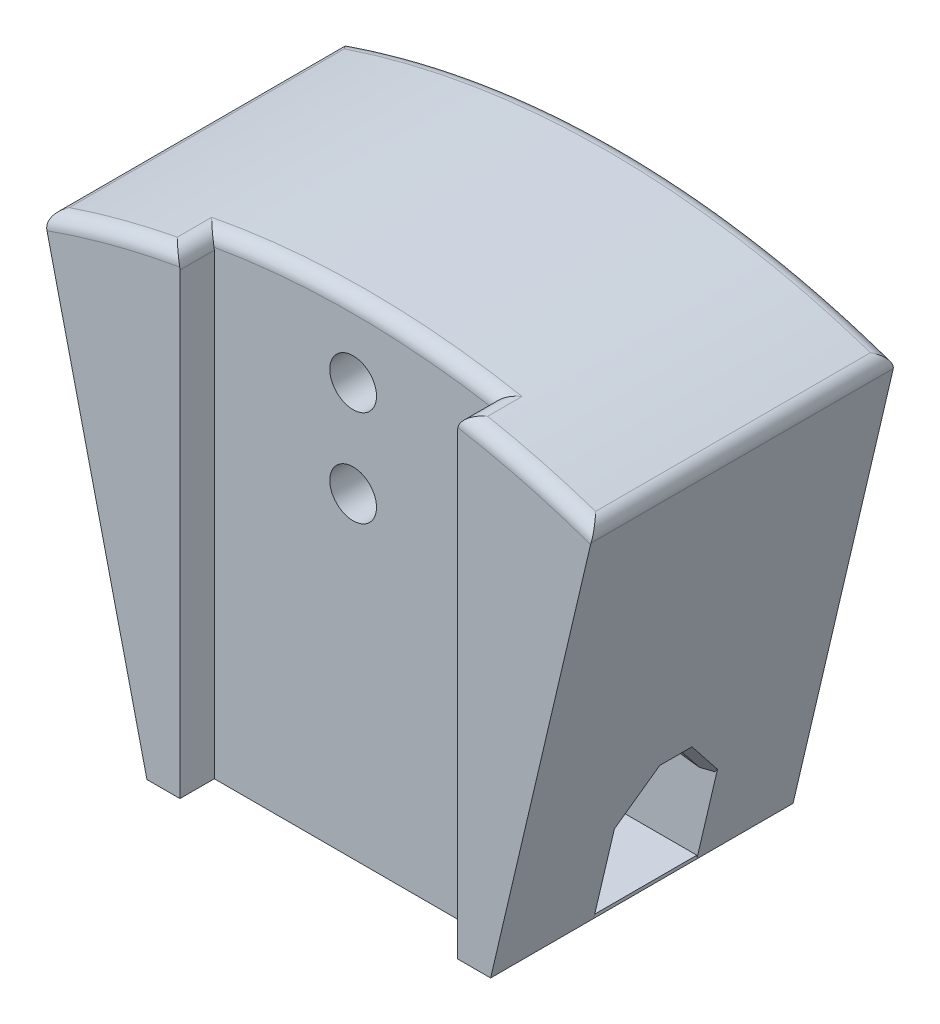
SolidWorks part; units mm, degrees
ref_plane "Front Plane" through (0, 0, 0) normal (0, 0, 1) x (1, 0, 0)
ref_plane "Top Plane" through (0, 0, 0) normal (0, 1, 0) x (1, 0, 0)
ref_plane "Right Plane" through (0, 0, 0) normal (1, 0, 0) x (0, 0, -1)
sketch "Sketch1" plane through (0, 0, 0) normal (0, 0, 1) x (1, 0, 0)
  line L3 (-15.875, -12.7) -> (-25.4, 27.8365)
  line L6 (15.875, -12.7) -> (-15.875, -12.7)
  line L8 (0, 0) -> (-15.875, -12.7) construction
  line L9 (15.875, -12.7) -> (0, 0) construction
  line L10 (15.875, -12.7) -> (25.4, 27.8365)
  line L12 (0, 0) -> (0, 32.1945) construction
  arc A0 (-25.4, 27.8365) -> (25.4, 27.8365) centre (0, -44.0055) cw
  point P3 (0, 0)
  point P8 (0, 0)
  point P12 (0, 32.1945)
  dimension "D1" = 32.1945
  dimension "D3" = 50.8
  dimension "D8" = 102.68
  dimension "D2" = 76.2
  dimension "D5" = 31.75
  dimension "D6" = 12.7
extrude "Boss-Extrude1" add sketch "Sketch1" along normal mid plane 27.94
sketch "Sketch5" plane through (0, 0, 13.97) normal (0, 0, 1) x (1, 0, 0)
  line L4 (0, -12.7) -> (0, 0) construction
  line L5 (-12.827, 0) -> (12.827, 0) construction
  line L8 (-12.827, 63.5) -> (-12.827, -12.7)
  line L9 (-12.827, -12.7) -> (12.827, -12.7)
  line L10 (12.827, -12.7) -> (12.827, 63.5)
  line L11 (12.827, 63.5) -> (-12.827, 63.5)
  point P9 (0, 0)
  dimension "D1" = 25.654
  dimension "D2" = 76.2
  dimension "D3" = 12.7
extrude "Cut-Extrude3" cut sketch "Sketch5" against normal blind 3.175
sketch "Sketch8" plane through (0, 0, 10.795) normal (0, 0, 1) x (1, 0, 0)
  line L0 (0, 25.4) -> (0, 0) construction
  circle A2 centre (0, 16.51) radius 2.159
  circle A4 centre (0, 25.4) radius 2.159
  dimension "D2" = 16.51
  dimension "D3" = 4.318
  dimension "D1" = 25.4
extrude "Cut-Extrude5" cut sketch "Sketch8" against normal through all both and the other way through all
ref_axis "Axis1" through (0, 0, 20.955) along (0, 0, -1)
sketch "Sketch6" plane through (0, 0, 0) normal (1, 0, 0) x (0, 0, -1)
  line L1 (-4.445, 13.97) -> (5.08, 13.97)
  line L5 (-20.955, 0) -> (20.955, 0) construction
  line L7 (5.08, 13.97) -> (5.08, 0)
  line L8 (5.08, 0) -> (-4.445, 0)
  line L9 (-4.445, 0) -> (-4.445, 13.97)
  line L11 (-10.795, 32.1945) -> (-10.795, 31.1071) construction
  dimension "D1" = 6.35
  dimension "D2" = 13.97
  dimension "D3" = 9.525
revolve "Cut-Revolve2" cut sketch "Sketch6" angle 360 about axis through (0, 0, 20.955) along (0, 0, -1)
ref_plane "Plane1" through (0, 0, -0.3175) normal (0, 0, -1) x (-1, 0, 0)
sketch "Sketch7" plane through (0, 0, -5.08) normal (0, 0, -1) x (-1, 0, 0)
  line L0 (12.8382, 5.5083) -> (17.5649, -5.5083)
  line L2 (-12.8382, 5.5083) -> (-17.5649, -5.5083)
  line L3 (25.4, 27.8365) -> (15.875, -12.7) construction
  line L5 (17.5649, -5.5083) -> (15.875, -12.7)
  line L6 (15.875, -12.7) -> (-15.875, -12.7)
  line L7 (-15.875, -12.7) -> (-17.5649, -5.5083)
  line L8 (-15.875, -12.7) -> (-25.4, 27.8365) construction
  line L9 (15.2015, 0) -> (-15.2015, 0) construction
  line L10 (-15.875, -12.7) -> (-25.4, 27.8365) construction
  arc A4 (5.8199, -12.7) -> (-5.8199, -12.7) centre (0, 0) ccw construction
  arc A5 (12.8382, 5.5083) -> (-12.8382, 5.5083) centre (0, 0) ccw
  point P29 (0, 0)
extrude "Cut-Extrude4" cut sketch "Sketch7" against normal up to surface (9.525 mm away) up to face at (0, 0.635, 4.445)
sketch "Sketch3" plane through (0, 0, -13.97) normal (0, 0, -1) x (-1, 0, 0)
  line L1 (6.5405, -3.7762) -> (6.5405, 3.7762)
  line L2 (6.5405, 3.7762) -> (0, 7.5523)
  line L3 (0, 7.5523) -> (-6.5405, 3.7762)
  line L4 (-6.5405, 3.7762) -> (-6.5405, -3.7762)
  line L5 (-6.5405, -3.7762) -> (0, -7.5523)
  line L6 (0, -7.5523) -> (6.5405, -3.7762)
  circle A1 centre (0, 0) radius 6.5405 construction
  dimension "D1" = 13.081
extrude "Cut-Extrude1" cut sketch "Sketch3" against normal offset from surface (22.225 mm away) 2.54 up to face at (2.159, 16.51, 10.795)
ref_plane "Plane2" through (0, 32.1945, 0) normal (0, 1, 0) x (1, 0, 0)
sketch "Sketch9" plane through (0, 0, -13.97) normal (0, 0, -1) x (-1, 0, 0)
  line L1 (3.625, 23.3071) -> (3.625, 27.4929)
  line L2 (3.625, 27.4929) -> (0, 29.5858)
  line L3 (0, 29.5858) -> (-3.625, 27.4929)
  line L4 (-3.625, 27.4929) -> (-3.625, 23.3071)
  line L5 (-3.625, 23.3071) -> (0, 21.2142)
  line L6 (0, 21.2142) -> (3.625, 23.3071)
  line L7 (3.625, 18.6029) -> (0, 20.6958)
  line L8 (0, 20.6958) -> (-3.625, 18.6029)
  line L9 (-3.625, 18.6029) -> (-3.625, 14.4171)
  line L10 (-3.625, 14.4171) -> (0, 12.3242)
  line L11 (0, 12.3242) -> (3.625, 14.4171)
  line L12 (3.625, 14.4171) -> (3.625, 18.6029)
  circle A0 centre (0, 25.4) radius 3.625 construction
  circle A1 centre (0, 16.51) radius 3.625 construction
  dimension "D1" = 7.25
extrude "Cut-Extrude6" cut sketch "Sketch9" against normal blind 5
sketch "Sketch10" plane through (0, 0, 0) normal (1, 0, 0) x (0, 0, -1)
  line L0 (-4.445, -5.5083) -> (-0.9525, -1.3461)
  line L1 (1.5875, -1.3461) -> (5.08, -5.5083)
  line L2 (0.3175, -5.5083) -> (0.3175, -1.3461) construction
  line L3 (-4.445, -5.5083) -> (5.08, -5.5083) construction
  line L4 (-0.9525, -1.3461) -> (1.5875, -1.3461)
  line L5 (-4.445, -5.5083) -> (5.08, -5.5083)
  dimension "D1" = 50
  dimension "D2" = 2.54
extrude "Cut-Extrude8" cut sketch "Sketch10" against normal through all both and the other way through all
chamfer "Chamfer1" distance 0.508 angle 45 6 edges at (-18.0539, -3.4272, 2.6988) (-18.0539, -3.4272, -3.3337) (-18.5429, -1.3461, -0.3175) (18.0539, -3.4272, -3.3337) (18.5429, -1.3461, -0.3175) (18.0539, -3.4272, 2.6988)
chamfer "Chamfer2" distance 0.508 angle 45 6 edges at (-16.5052, -3.0385, 2.3726) (-15.7791, -1.3461, -0.3175) (-16.5052, -3.0385, -3.0076) (16.5052, -3.0385, 2.3726) (15.7791, -1.3461, -0.3175) (16.5052, -3.0385, -3.0076)
fillet "Fillet2" radius 1.27 8 edges at (-12.827, 31.1071, 12.3825) (-19.1833, 29.7403, 13.97) (-25.4, 27.8365, 0) (0, 32.1945, -13.97) (25.4, 27.8365, 0) (19.1833, 29.7403, 13.97) (12.827, 31.1071, 12.3825) (0, 32.1945, 10.795)
sketch "Sketch11" plane through (0, -12.7, 0) normal (0, -1, 0) x (1, 0, 0)
  line L1 (15.875, 4.445) -> (-15.875, 4.445)
  line L2 (15.875, 4.445) -> (15.875, -5.08)
  line L3 (15.875, -5.08) -> (-15.875, -5.08)
  line L4 (-15.875, 4.445) -> (-15.875, -5.08)
extrude "Boss-Extrude3" add sketch "Sketch11" against normal blind 0.3
